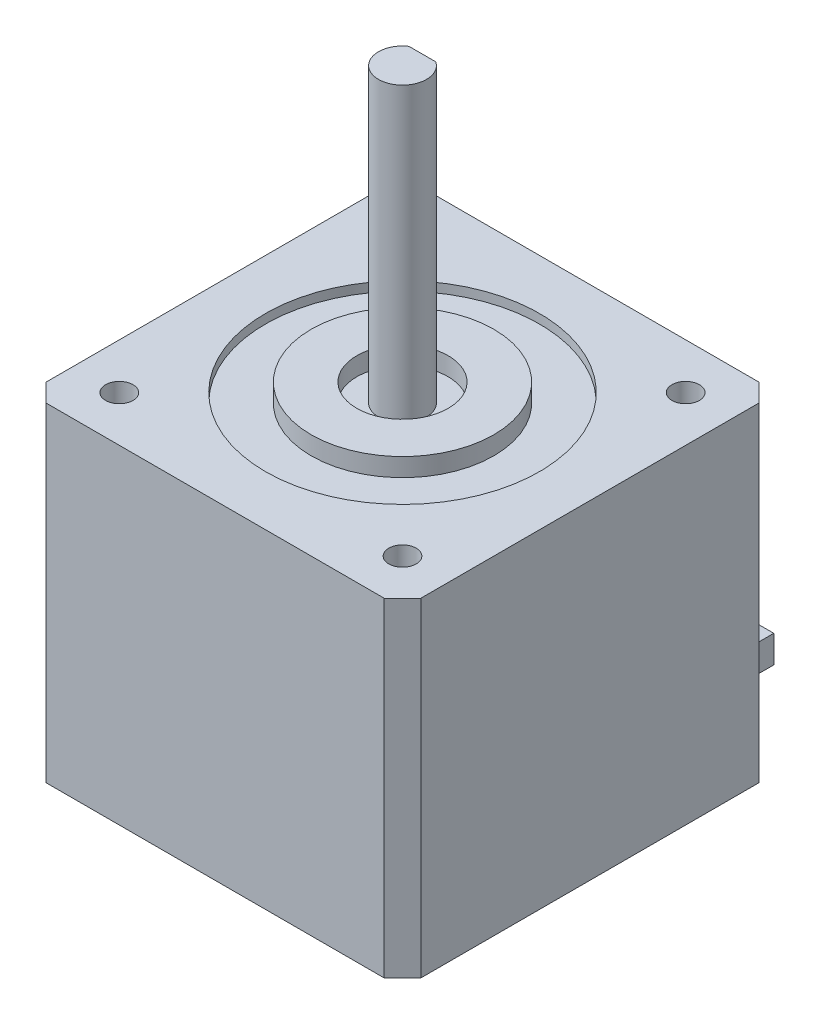
SolidWorks part; units mm, degrees
ref_plane "Front Plane" through (0, 0, 0) normal (0, 0, 1) x (1, 0, 0)
ref_plane "Top Plane" through (0, 0, 0) normal (0, 1, 0) x (1, 0, 0)
ref_plane "Right Plane" through (0, 0, 0) normal (1, 0, 0) x (0, 0, -1)
sketch "Sketch1" plane through (0, 0, 0) normal (0, 1, 0) x (1, 0, 0)
  line L0 (-20.5, 18.5) -> (-18.5, 20.5)
  line L1 (-18.5, -20.5) -> (18.5, -20.5)
  line L2 (-20.5, -18.5) -> (-20.5, 18.5)
  line L3 (-18.5, 20.5) -> (18.5, 20.5)
  line L4 (20.5, -18.5) -> (20.5, 18.5)
  line L5 (-20.5, -20.5) -> (20.5, 20.5) construction
  line L6 (-20.5, 20.5) -> (20.5, -20.5) construction
  line L7 (-18.5, -20.5) -> (-20.5, -18.5)
  line L8 (18.5, -20.5) -> (20.5, -18.5)
  line L9 (20.5, 18.5) -> (18.5, 20.5)
  point P0 (0, 0)
  dimension "D1" = 41
  dimension "D2" = 41
extrude "Boss-Extrude1" add sketch "Sketch1" along normal blind 36
sketch "Sketch2" plane through (0, 36, 0) normal (0, 1, 0) x (-1, 0, 0)
  circle A0 centre (0, 0) radius 15
extrude "Cut-Extrude1" cut sketch "Sketch2" against normal blind 1
sketch "Sketch3" plane through (0, 35, 0) normal (0, 1, 0) x (1, 0, 0)
  circle A0 centre (0, 0) radius 10
  circle A1 centre (0, 0) radius 5
extrude "Boss-Extrude2" add sketch "Sketch3" along normal blind 2
sketch "Sketch4" plane through (0, 35, 0) normal (0, 1, 0) x (1, 0, 0)
  line L0 (-1.471, 2.1754) -> (1.471, 2.1754)
  arc A0 (-1.471, 2.1754) -> (1.471, 2.1754) centre (0, 0) ccw
extrude "Boss-Extrude3" add sketch "Sketch4" along normal blind 32
hole_wizard "Ø3.0 (3) Diameter Hole1" positions "Sketch6" profile "Sketch5" hole size "Ø3.0" standard "Ansi Metric"
sketch "Sketch6" plane through (0, 36, 0) normal (0, 1, 0) x (-1, 0, 0)
  arc A0 (1.471, -2.1754) -> (-1.471, -2.1754) centre (0, 0) ccw construction
  point P0 (-15.5, -15.5)
  point P1 (15.5, -15.5)
  point P3 (15.5, 15.5)
  point P5 (-15.5, 15.5)
  dimension "D3" = 15.5
  dimension "D1" = 31
  dimension "D2" = 31
  dimension "D4" = 15.5
sketch "Sketch5" plane through (15.5, 36, -15.5) normal (1, 0, 0) x (0, 0, 1)
  line L0 (0, 0) -> (0, 5.9013)
  line L1 (0, 5.9013) -> (1.5, 5)
  line L2 (1.5, 5) -> (1.5, 0)
  line L5 (1.5, 0) -> (0, 0)
  line L10 (0, 5.9013) -> (-1.5, 5) construction
  line L11 (0, -6.35) -> (0, 107.95) construction
  dimension "Hole Dia." = 3
  dimension "Hole Depth" = 5
  dimension "Drill Angle" = 118
ref_axis "Motor Axis" through (0, 67, 0) along (0, -1, 0)
sketch "Sketch7" plane through (0, 0, -20.5) normal (0, 0, -1) x (-1, 0, 0)
  line L0 (-18.5, 0) -> (18.5, 0) construction
  line L1 (-10.1415, 0) -> (9.8585, 0)
  line L2 (-10.1415, 0) -> (-10.1415, 3)
  line L3 (-10.1415, 3) -> (9.8585, 3)
  line L4 (9.8585, 0) -> (9.8585, 3)
  dimension "D1" = 20
  dimension "D2" = 3
extrude "Boss-Extrude4" add sketch "Sketch7" along normal blind 10
